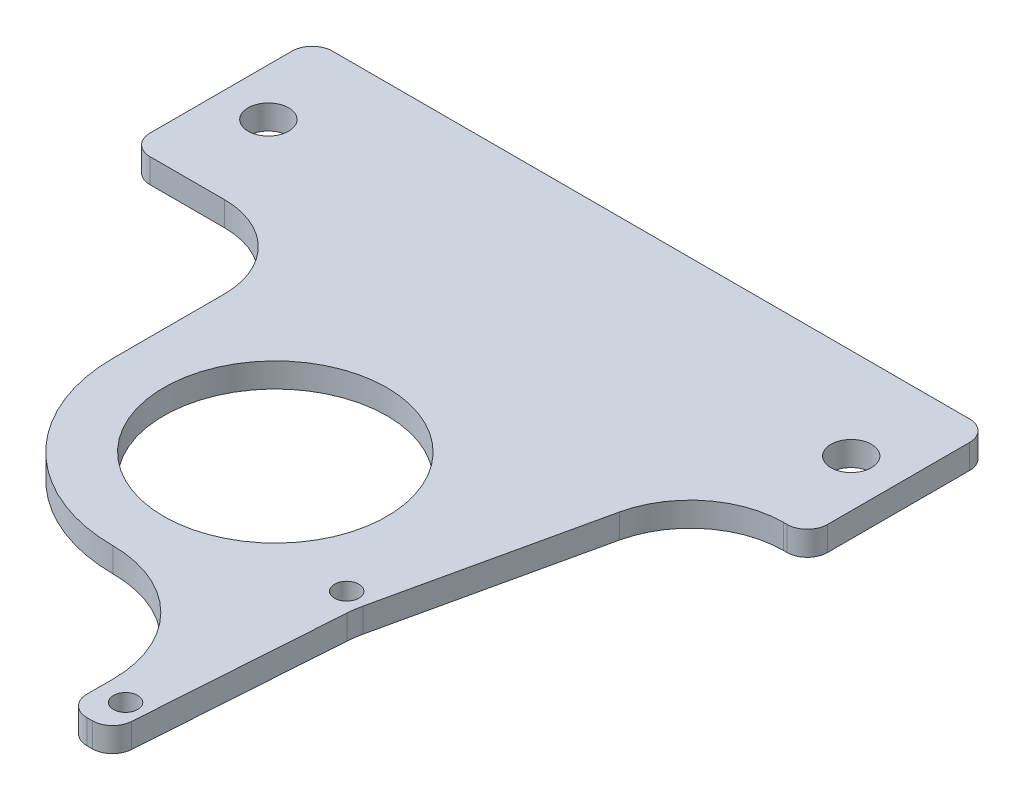
SolidWorks part; units mm, degrees
ref_plane "Front Plane" through (0, 0, 0) normal (0, 0, 1) x (1, 0, 0)
ref_plane "Top Plane" through (0, 0, 0) normal (0, 1, 0) x (1, 0, 0)
ref_plane "Right Plane" through (0, 0, 0) normal (1, 0, 0) x (0, 0, -1)
sketch "Sketch1" plane through (0, 0, 0) normal (0, 1, 0) x (1, 0, 0)
  line L10 (-83.5, 92.6) -> (83.5, 92.6)
  line L11 (77.8333, 47.6) -> (30.5, 47.6) construction
  line L12 (83.5, 50.6) -> (83.5, 63.8) construction
  line L13 (83.5, 92.6) -> (83.5, 47.6)
  line L14 (-83.5, 92.6) -> (-83.5, 47.6)
  line L15 (35, -71.9) -> (38.5, -20.9) construction
  line L16 (39.7824, -75.2423) -> (43.1965, -25.4933)
  line L17 (83.5, 47.6) -> (77.6499, 47.6)
  line L18 (55.2, 29.6) -> (43.6926, -22.068)
  line L19 (39.9883, -72.2423) -> (43.4883, -21.2423) construction
  line L20 (-67.3757, 92.6) -> (-80.5, 92.6) construction
  line L21 (34.7941, -79.9) -> (33.4627, -79.9)
  line L23 (-60.1247, 47.6) -> (-83.5, 47.6)
  line L24 (-40, 0) -> (-40, 27.4753)
  line L25 (28.4627, -74.9) -> (28.4627, -68.4627)
  line L26 (-71.8123, 47.6) -> (-71.8123, 92.6) construction
  line L27 (0, -55) -> (0, 55) construction
  line L28 (71.8123, 47.6) -> (71.8123, 92.6) construction
  line L29 (-60.1247, 47.6) -> (-60.1247, -109.4) construction
  line L30 (-30.5, 47.6) -> (-75, 47.6) construction
  line L31 (-83.5, 63.8) -> (-83.5, 50.6) construction
  line L32 (65, 29.6) -> (45.4, 29.6) construction
  circle A0 centre (0, 0) radius 27.5
  circle A1 centre (38.5, -20.9) radius 3
  circle A2 centre (35, -71.9) radius 3
  arc A3 (-40, 0) -> (0, -40) centre (0, 0) ccw
  arc A4 (-40, 27.4753) -> (-60.1247, 47.6) centre (-60.1247, 27.4753) ccw
  arc A5 (0, -40) -> (28.4627, -68.4627) centre (0, -68.4627) cw
  arc A6 (77.6499, 47.6) -> (55.2, 29.6) centre (77.6499, 24.6) ccw
  arc A7 (43.1965, -25.4933) -> (43.6926, -22.068) centre (66.1426, -27.068) cw
  arc A8 (33.4627, -79.9) -> (28.4627, -74.9) centre (33.4627, -74.9) cw
  arc A9 (34.7941, -79.9) -> (39.7824, -75.2423) centre (34.7941, -74.9) ccw
  circle A10 centre (-71.8123, 70.1) radius 5
  circle A11 centre (71.8123, 70.1) radius 5
  point P7 (-81.2345, 52.6)
  point P8 (-60.1247, 43.8968)
  point P13 (0, 0)
  point P14 (0, 0)
  point P38 (59.2089, 47.6)
  point P44 (28.4627, -79.9)
  point P47 (39.4627, -79.9)
  point P54 (-83.5, 70.1)
  point P62 (0, 0)
  point P63 (-71.8123, 70.1)
  point P64 (55.2, 29.6)
  point P66 (-71.8123, 70.1)
  dimension "D1" = 55
  dimension "D3" = 80
  dimension "D5" = 23
  dimension "D8" = 5
  dimension "D9" = 6
  dimension "D10" = 10
  dimension "D4" = 11
  dimension "D6" = 8
  dimension "D2" = 5
extrude "Boss-Extrude1" add sketch "Sketch1" along normal blind 6
fillet "Fillet1" radius 5 4 edges at (83.5, 3, -47.6) (83.5, 3, -92.6) (-83.5, 3, -92.6) (-83.5, 3, -47.6)
